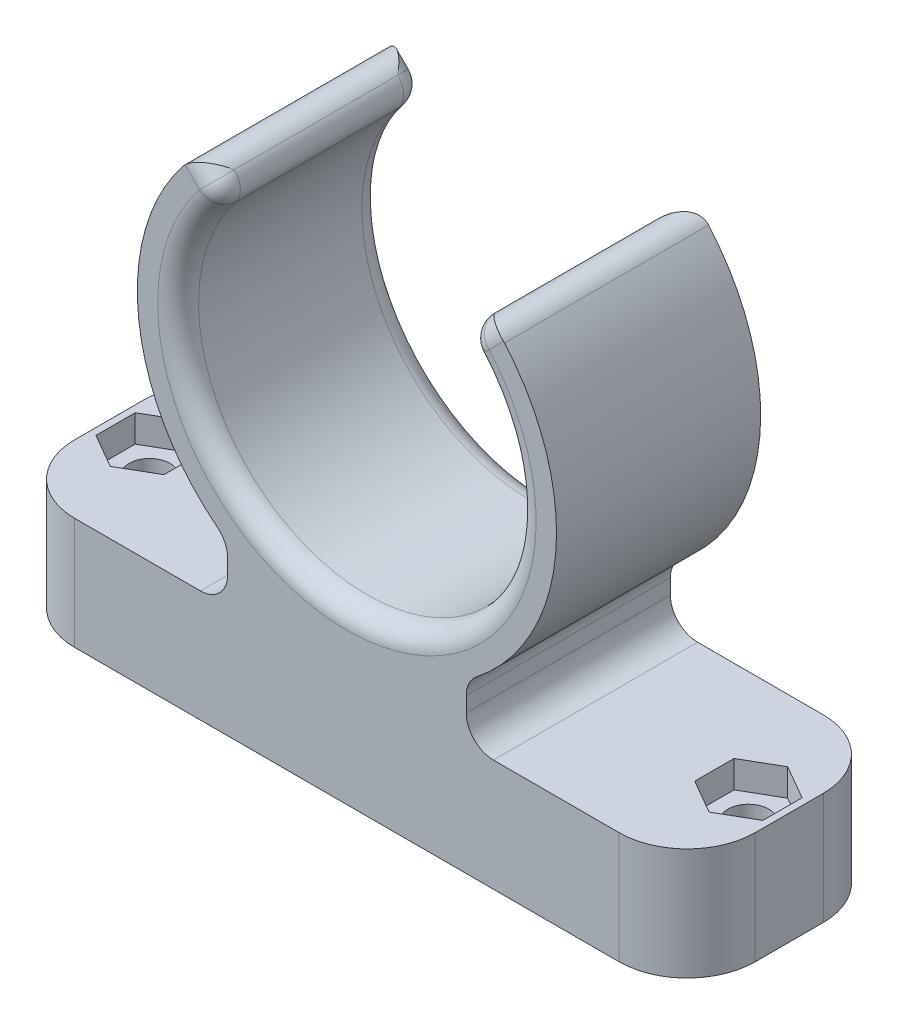
SolidWorks part; units mm, degrees
ref_plane "Plano frontal" through (0, 0, 0) normal (0, 0, 1) x (1, 0, 0)
ref_plane "Plano superior" through (0, 0, 0) normal (0, 1, 0) x (1, 0, 0)
ref_plane "Plano direito" through (0, 0, 0) normal (1, 0, 0) x (0, 0, -1)
sketch "Esboço2" plane through (0, 0, 0) normal (0, 0, 1) x (1, 0, 0)
  line L0 (0, 0) -> (0, -12.6) construction
  line L1 (-25, -12.6) -> (25, -12.6)
  line L2 (25, -12.6) -> (25, -4.3803)
  line L3 (-25, -4.3803) -> (-8.7681, -4.3803)
  line L4 (8.3328, 21.5828) -> (25, 38.25)
  line L5 (0, 0) -> (0, 12.4) construction
  line L6 (25, 38.25) -> (25, -4.3803) construction
  line L7 (-8.7681, 21.1681) -> (-10.8894, 23.2894)
  line L8 (-25, -12.6) -> (-25, -4.3803)
  line L9 (25, -4.3803) -> (8.7681, -4.3803)
  line L10 (-8.7681, -0.2602) -> (-8.7681, -4.3803)
  line L11 (8.7681, -0.2602) -> (8.7681, -4.3803)
  line L12 (25, -4.3803) -> (8.7681, -4.3803)
  arc A0 (-8.7681, 21.1681) -> (8.3328, 21.5828) centre (0, 12.4) ccw
  arc A1 (-10.8894, 23.2894) -> (-8.7681, -0.2602) centre (0, 12.4) ccw
  arc A2 (8.7681, -0.2602) -> (10.4561, 23.7061) centre (0, 12.4) ccw
  arc A3 (8.7681, -0.2602) -> (-8.7681, -0.2602) centre (0, 12.4) ccw
  point P7 (0, -9.4647)
  dimension "D4" = 12.4
  dimension "D5" = 3
  dimension "D1" = 25
  dimension "D2" = 45
  dimension "D3" = 50
  dimension "D6" = 8.2197
extrude "Ressalto-extrusão1" add sketch "Esboço2" along normal blind 15 contours A2 L4 A0 L7 A1 L8 L1 L2 region at (0.0267, -3.0177, 0)
sketch "Esboço3" plane through (0, -4.3803, 0) normal (0, 1, 0) x (1, 0, 0)
  line L0 (0, 0) -> (0, -15) construction
  line L1 (-25, 0) -> (25, 0) construction
  line L2 (-25, -15) -> (25, -15) construction
  line L3 (22, -15) -> (22, 0) construction
  line L5 (25, -15) -> (25, 0) construction
  circle A0 centre (22, -7.5) radius 1.5
  circle A1 centre (-22, -7.5) radius 1.5
  dimension "D1" = 3
extrude "Corte-extrusão1" cut sketch "Esboço3" against normal up to surface (8.2197 mm away) up to face at (0, -12.6, 7.5)
sketch "Esboço5" plane through (0, -4.3803, 0) normal (0, 1, 0) x (1, 0, 0)
  line L1 (22, -4.6132) -> (19.5, -6.0566)
  line L2 (19.5, -6.0566) -> (19.5, -8.9434)
  line L3 (19.5, -8.9434) -> (22, -10.3868)
  line L4 (22, -10.3868) -> (24.5, -8.9434)
  line L5 (24.5, -8.9434) -> (24.5, -6.0566)
  line L6 (24.5, -6.0566) -> (22, -4.6132)
  line L7 (0, 0) -> (0, -14.5158)
  line L8 (-24.5, -6.0566) -> (-22, -4.6132)
  line L9 (-24.5, -8.9434) -> (-24.5, -6.0566)
  line L10 (-22, -10.3868) -> (-24.5, -8.9434)
  line L11 (-19.5, -8.9434) -> (-22, -10.3868)
  line L12 (-19.5, -6.0566) -> (-19.5, -8.9434)
  line L13 (-22, -4.6132) -> (-19.5, -6.0566)
  circle A1 centre (22, -7.5) radius 1.5
  circle A2 centre (22, -7.5) radius 2.5 construction
  circle A3 centre (-22, -7.5) radius 2.5 construction
  circle A4 centre (-22, -7.5) radius 1.5
extrude "Corte-extrusão2" cut sketch "Esboço5" against normal blind 2 contours L5 L6 L1 L2 L3 L4 | L13 L8 L9 L10 L11 L12 A4 region at (23.2118, -4.3803, 5.4011) region at (-23.2118, -4.3803, 5.4011)
fillet "Filete1" radius 1.5 10 edges at (0.3006, 0.0036, 15) (0.3006, 0.0036, 0) (10.4561, 23.7061, 7.5) (9.3945, 22.6445, 15) (8.3328, 21.5828, 7.5) (9.3945, 22.6445, 0) (-8.7681, 21.1681, 7.5) (-9.8288, 22.2288, 15) (-10.8894, 23.2894, 7.5) (-9.8288, 22.2288, 0)
fillet "Filete2" radius 2 4 edges at (8.7681, -0.2602, 7.5) (8.7681, -4.3803, 7.5) (-8.7681, -0.2602, 7.5) (-8.7681, -4.3803, 7.5)
fillet "Filete3" radius 5 4 edges at (25, -8.4902, 0) (25, -8.4902, 15) (-25, -8.4902, 0) (-25, -8.4902, 15)
